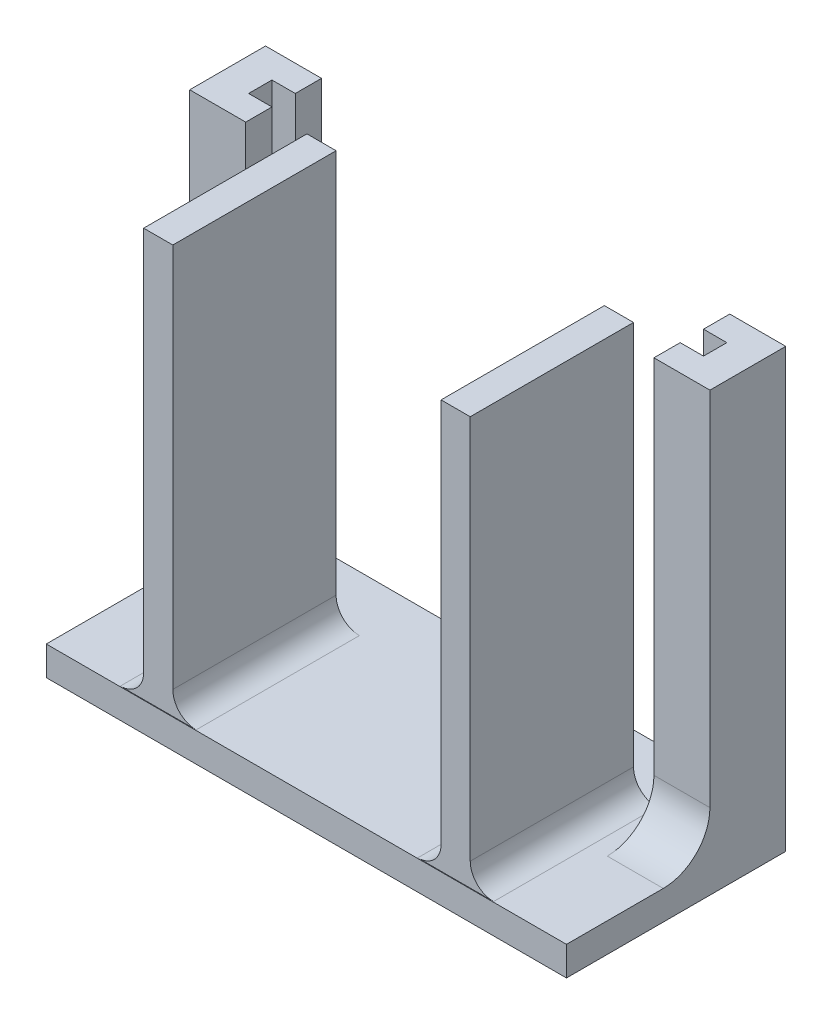
SolidWorks part; units mm, degrees
ref_plane "Front Plane" through (0, 0, 0) normal (0, 0, 1) x (1, 0, 0)
ref_plane "Top Plane" through (0, 0, 0) normal (0, 1, 0) x (1, 0, 0)
ref_plane "Right Plane" through (0, 0, 0) normal (1, 0, 0) x (0, 0, -1)
ref_plane "Plane1" through (0, -19, 0) normal (0, 1, 0) x (1, 0, 0)
sketch "Sketch1" plane through (0, -19, 0) normal (0, 1, 0) x (1, 0, 0)
  line L0 (0, 0) -> (0, -21.3085) construction
  line L1 (-19.5, 0.5) -> (-17.5, 0.5)
  line L2 (-17.5, 0.5) -> (-17.5, 2.75)
  line L3 (-17.5, 2.75) -> (-22.3, 2.75)
  line L4 (-22.3, 2.75) -> (-22.3, -3.75)
  line L5 (-22.3, -3.75) -> (-17.5, -3.75)
  line L6 (-17.5, -3.75) -> (-17.5, -1.5)
  line L7 (-17.5, -1.5) -> (-19.5, -1.5)
  line L8 (-19.5, -1.5) -> (-19.5, 0.5)
  line L10 (19.5, -1.5) -> (19.5, 0.5)
  line L11 (17.5, -1.5) -> (19.5, -1.5)
  line L12 (17.5, -3.75) -> (17.5, -1.5)
  line L13 (22.3, -3.75) -> (17.5, -3.75)
  line L14 (22.3, 2.75) -> (22.3, -3.75)
  line L15 (17.5, 2.75) -> (22.3, 2.75)
  line L16 (17.5, 0.5) -> (17.5, 2.75)
  line L17 (19.5, 0.5) -> (17.5, 0.5)
  line L18 (11.5, -2) -> (11.5, -16)
  line L19 (-14, -2) -> (-11.5, -2)
  line L20 (-14, -2) -> (-14, -16)
  line L21 (-14, -16) -> (-11.5, -16)
  line L22 (-11.5, -2) -> (-11.5, -16)
  line L23 (14, -16) -> (11.5, -16)
  line L24 (14, -2) -> (14, -16)
  line L25 (14, -2) -> (11.5, -2)
  dimension "D1" = 2
  dimension "D2" = 17.5
  dimension "D3" = 4.8
  dimension "D4" = 2.25
  dimension "D5" = 0.5
  dimension "D6" = 2
  dimension "D7" = 6.5
  dimension "D8" = 14
  dimension "D9" = 2
  dimension "D10" = 2.5
  dimension "D11" = 11.5
extrude "Boss-Extrude1" add sketch "Sketch1" along normal blind 35
sketch "Sketch2" plane through (0, -19, 0) normal (0, 1, 0) x (1, 0, 0)
  line L1 (-22.3, 2.75) -> (22.3, 2.75)
  line L2 (-22.3, 2.75) -> (-22.3, -16.05)
  line L3 (-22.3, -16.05) -> (22.3, -16.05)
  line L4 (22.3, 2.75) -> (22.3, -16.05)
  dimension "D1" = 44.6
  dimension "D2" = 18.8
extrude "Boss-Extrude2" add sketch "Sketch2" against normal blind 2.5
fillet "Fillet1" radius 2 4 edges at (-14, -19, 9) (11.5, -19, 9) (-11.5, -19, 9) (14, -19, 9)
fillet "Fillet2" radius 4 2 edges at (19.9, -19, 3.75) (-19.9, -19, 3.75)
